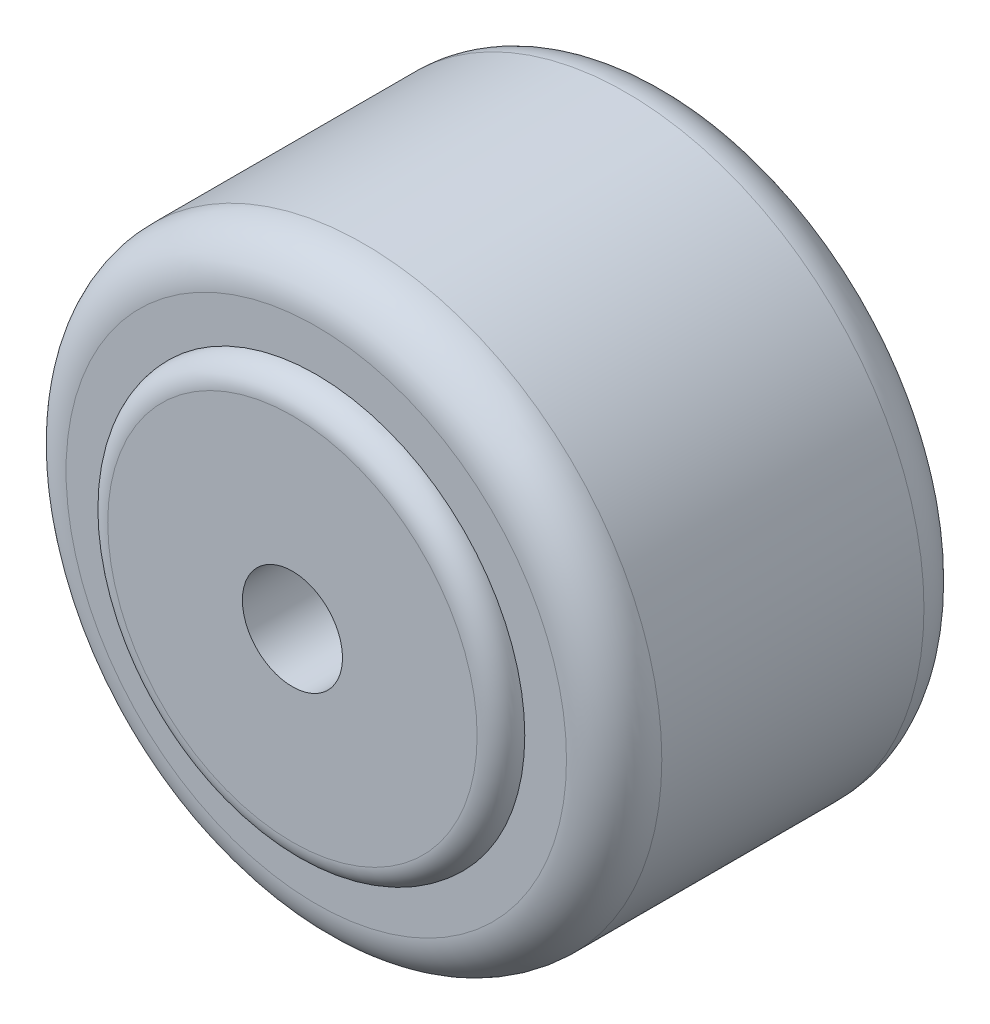
SolidWorks part; units mm, degrees
ref_plane "前视基准面" through (0, 0, 0) normal (0, 0, 1) x (1, 0, 0)
ref_plane "上视基准面" through (0, 0, 0) normal (0, 1, 0) x (1, 0, 0)
ref_plane "右视基准面" through (0, 0, 0) normal (1, 0, 0) x (0, 0, -1)
sketch "草图1" plane through (0, 0, 0) normal (0, 0, 1) x (1, 0, 0)
  circle A0 centre (0, 0) radius 25
  dimension "D1" = 50
extrude "凸台-拉伸1" add sketch "草图1" along normal blind 30
fillet "圆角1" radius 4 1 edges at (25, 0, 30)
fillet "圆角2" radius 4 1 edges at (25, 0, 0)
sketch "草图2" plane through (0, 0, 30) normal (0, 0, 1) x (1, 0, 0)
  circle A0 centre (0, 0) radius 17.5
  circle A1 centre (0, 0) radius 21 construction
  dimension "35" = 35
extrude "凸台-拉伸2" add sketch "草图2" along normal blind 2
fillet "圆角3" radius 2 1 edges at (17.5, 0, 32)
sketch "草图3" plane through (0, 0, 0) normal (0, 0, -1) x (-1, 0, 0)
  circle A0 centre (0, 0) radius 17.5
  circle A1 centre (0, 0) radius 21 construction
  dimension "35" = 35
extrude "凸台-拉伸3" add sketch "草图3" along normal blind 2
fillet "圆角4" radius 2 1 edges at (-17.5, 0, -2)
sketch "草图4" plane through (0, 0, -2) normal (0, 0, -1) x (-1, 0, 0)
  circle A0 centre (0, 0) radius 4.2
  dimension "D1" = 8.4
extrude "切除-拉伸1" cut sketch "草图4" against normal through all
